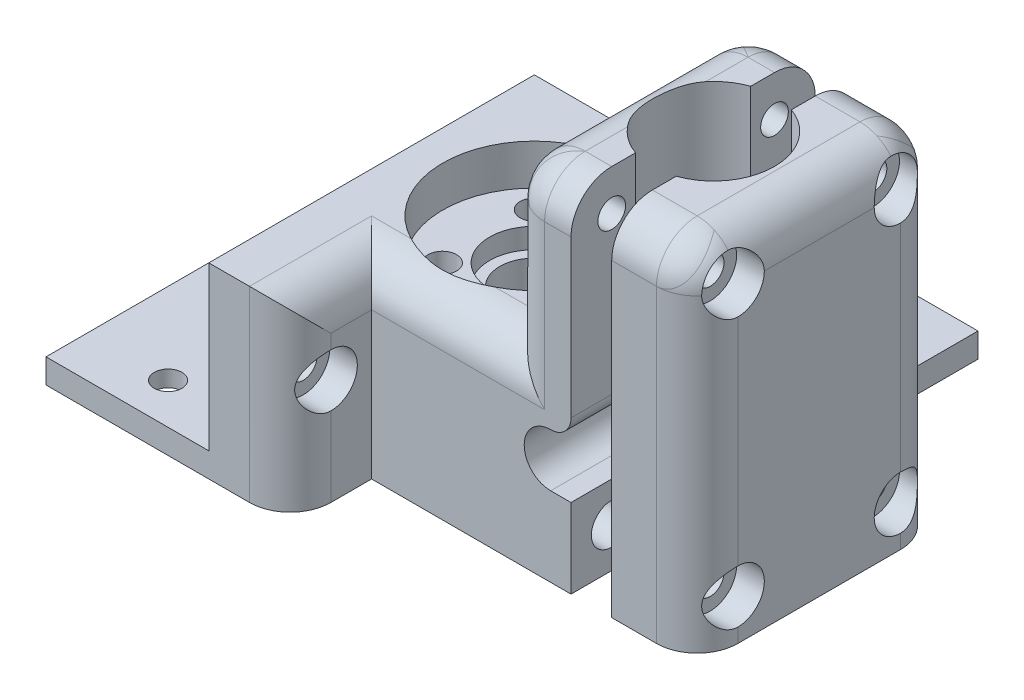
SolidWorks part; units mm, degrees
material "ABS"
ref_plane "Front Plane" through (0, 0, 0) normal (0, 0, 1) x (1, 0, 0)
ref_plane "Top Plane" through (0, 0, 0) normal (0, 1, 0) x (1, 0, 0)
ref_plane "Right Plane" through (0, 0, 0) normal (1, 0, 0) x (0, 0, -1)
sketch "Sketch1" plane through (0, 0, 0) normal (1, 0, 0) x (0, 0, -1)
  line L1 (-15, -10) -> (15, -10)
  line L2 (-15, -10) -> (-15, 10)
  line L3 (-15, 10) -> (15, 10)
  line L4 (15, -10) -> (15, 10)
  line L5 (-15, -10) -> (15, 10) construction
  line L6 (-15, 10) -> (15, -10) construction
  point P0 (0, 0)
  dimension "D1" = 30
  dimension "D2" = 20
extrude "Boss-Extrude1" add sketch "Sketch1" along normal blind 50
sketch "Sketch2" plane through (0, 10, 0) normal (0, 1, 0) x (1, 0, 0)
  line L0 (0, 15) -> (0, -15) construction
  circle A0 centre (15, 0) radius 4.25
  circle A1 centre (37, 0) radius 7.5
  dimension "D1" = 8.5
  dimension "D3" = 15
  dimension "D2" = 22
  dimension "D4" = 15
extrude "Cut-Extrude1" cut sketch "Sketch2" against normal through all
sketch "Sketch4" plane through (0, 10, 0) normal (0, 1, 0) x (1, 0, 0)
  circle A0 centre (15, 0) radius 11.25
  dimension "D1" = 22.5
extrude "Cut-Extrude3" cut sketch "Sketch4" against normal blind 5
sketch "Sketch5" plane through (0, 5, 0) normal (0, 1, 0) x (1, 0, 0)
  line L1 (20.6569, -5.6569) -> (9.3431, -5.6569) construction
  line L2 (20.6569, -5.6569) -> (20.6569, 5.6569) construction
  line L3 (20.6569, 5.6569) -> (9.3431, 5.6569) construction
  line L4 (9.3431, -5.6569) -> (9.3431, 5.6569) construction
  line L5 (20.6569, -5.6569) -> (9.3431, 5.6569) construction
  line L6 (20.6569, 5.6569) -> (9.3431, -5.6569) construction
  circle A3 centre (9.3431, -5.6569) radius 1.75
  circle A4 centre (9.3431, 5.6569) radius 1.75
  circle A5 centre (20.6569, 5.6569) radius 1.75
  circle A6 centre (20.6569, -5.6569) radius 1.75
  point P0 (15, 0)
  dimension "D1" = 16
  dimension "D3" = 3.5
  dimension "D4" = 3.5
  dimension "D5" = 3.5
  dimension "D6" = 3.5
extrude "Cut-Extrude4" cut sketch "Sketch5" against normal through all
sketch "Sketch6" plane through (0, -10, 0) normal (0, -1, 0) x (1, 0, 0)
  line L1 (12.8058, 5.7559) -> (10.9887, 8.7052)
  line L2 (10.9887, 8.7052) -> (7.526, 8.6061)
  line L3 (7.526, 8.6061) -> (5.8805, 5.5578)
  line L4 (5.8805, 5.5578) -> (7.6976, 2.6085)
  line L5 (7.6976, 2.6085) -> (11.1603, 2.7076)
  line L6 (11.1603, 2.7076) -> (12.8058, 5.7559)
  line L7 (17.1942, 5.7559) -> (18.8397, 2.7076)
  line L8 (18.8397, 2.7076) -> (22.3024, 2.6085)
  line L9 (22.3024, 2.6085) -> (24.1195, 5.5578)
  line L10 (24.1195, 5.5578) -> (22.474, 8.6061)
  line L11 (22.474, 8.6061) -> (19.0113, 8.7052)
  line L12 (19.0113, 8.7052) -> (17.1942, 5.7559)
  line L13 (24.1197, -5.7506) -> (22.4694, -2.7048)
  line L14 (22.4694, -2.7048) -> (19.0066, -2.6111)
  line L15 (19.0066, -2.6111) -> (17.194, -5.5631)
  line L16 (17.194, -5.5631) -> (18.8443, -8.6089)
  line L17 (18.8443, -8.6089) -> (22.3071, -8.7026)
  line L18 (22.3071, -8.7026) -> (24.1197, -5.7506)
  line L19 (12.8058, -5.7559) -> (11.1603, -2.7076)
  line L20 (11.1603, -2.7076) -> (7.6976, -2.6085)
  line L21 (7.6976, -2.6085) -> (5.8805, -5.5578)
  line L22 (5.8805, -5.5578) -> (7.526, -8.6061)
  line L23 (7.526, -8.6061) -> (10.9887, -8.7052)
  line L24 (10.9887, -8.7052) -> (12.8058, -5.7559)
  circle A0 centre (9.3431, 5.6569) radius 3 construction
  circle A1 centre (20.6569, 5.6569) radius 3 construction
  circle A2 centre (20.6569, -5.6569) radius 3 construction
  circle A3 centre (9.3431, -5.6569) radius 3 construction
  dimension "D1" = 6
  dimension "D2" = 6
  dimension "D4" = 6
  dimension "D3" = 6
extrude "Cut-Extrude5" cut sketch "Sketch6" against normal blind 6
ref_plane "Plane1" through (0, 0, 0) normal (0, 0, -1) x (-1, 0, 0)
sketch "Sketch7" plane through (0, 0, 15) normal (0, 0, 1) x (1, 0, 0)
  line L0 (50, -10) -> (0, -10) construction
  line L1 (0, 10) -> (10, 10)
  line L2 (0, 10) -> (0, -10)
  line L3 (0, -10) -> (10, -10)
  line L4 (10, 10) -> (10, -10)
  dimension "D1" = 10
extrude "Boss-Extrude2" add sketch "Sketch7" along normal blind 10
hole_wizard "CBORE for M3 Hex Socket Head Cap Screw4" positions "Sketch16" profile "Sketch17" counterbore size "M3" standard "ISO" end condition through all
sketch "Sketch16" plane through (10, 0, 0) normal (1, 0, 0) x (0, 0, -1)
  line L0 (-25, -10) -> (-25, 10) construction
  point P0 (-20, 0)
  dimension "D1" = 5
sketch "Sketch17" plane through (10, 0, 20) normal (0, 1, 0) x (0, 0, -1)
  line L0 (0, 0) -> (0, 10)
  line L1 (0, 10) -> (1.7, 10)
  line L3 (1.7, 10) -> (1.7, 3.4)
  line L4 (1.7, 3.4) -> (3.25, 3.4)
  line L5 (3.25, 3.4) -> (3.25, 0)
  line L7 (3.25, 0) -> (0, 0)
  line L11 (0, -6.35) -> (0, 107.95) construction
  dimension "Thru Hole Dia." = 3.4
  dimension "Thru Hole Depth" = 10
  dimension "C'Bore Dia." = 6.5
  dimension "C'Bore Depth" = 3.4
sketch "Sketch19" plane through (0, 5, 0) normal (0, 1, 0) x (1, 0, 0)
  circle A0 centre (15, 0) radius 5.5
  dimension "D1" = 11
extrude "Cut-Extrude10" cut sketch "Sketch19" against normal blind 2.5
hole_wizard "CBORE for M3 Hex Socket Head Cap Screw5" positions "Sketch22" profile "Sketch24" counterbore size "M3" standard "ISO" end condition through all
sketch "Sketch22" plane through (0, 0, 15) normal (0, 0, 1) x (1, 0, 0)
  line L0 (50, -10) -> (10, -10) construction
  point P0 (32, 0)
  dimension "D1" = 10
  dimension "D2" = 2.5
sketch "Sketch24" plane through (32, 0, 15) normal (1, 0, 0) x (0, -1, 0)
  line L0 (0, 0) -> (0, 30)
  line L1 (0, 30) -> (1.7, 30)
  line L3 (1.7, 30) -> (1.7, 26.4)
  line L4 (1.7, 26.4) -> (3.25, 26.4)
  line L5 (3.25, 26.4) -> (3.25, 0)
  line L7 (3.25, 0) -> (0, 0)
  line L11 (0, -6.35) -> (0, 107.95) construction
  dimension "Thru Hole Dia." = 3.4
  dimension "Thru Hole Depth" = 30
  dimension "C'Bore Dia." = 6.5
  dimension "C'Bore Depth" = 26.4
sketch "Sketch26" plane through (0, 10, 0) normal (0, 1, 0) x (1, 0, 0)
  line L0 (50, 15) -> (0, 15) construction
  line L1 (50, -15) -> (26.25, -15)
  line L2 (50, -15) -> (50, 15)
  line L3 (50, 15) -> (26.25, 15)
  line L4 (26.25, -15) -> (26.25, 15)
  circle A0 centre (15, 0) radius 11.25 construction
extrude "Boss-Extrude3" add sketch "Sketch26" along normal blind 20
sketch "Sketch43" plane through (0, -10, 0) normal (0, -1, 0) x (1, 0, 0)
  line L6 (0, 25) -> (0, -15)
  line L7 (0, -15) -> (50, -15)
  line L8 (50, -15) -> (50, 15)
  line L9 (50, 15) -> (10, 15)
  line L10 (10, 15) -> (10, 25)
  line L11 (10, 25) -> (0, 25)
  line L12 (0, 25) -> (0, -15)
  line L13 (0, -15) -> (50, -15)
  line L14 (50, -15) -> (50, 15)
  line L15 (50, 15) -> (10, 15)
  line L16 (10, 15) -> (10, 25)
  line L17 (10, 25) -> (0, 25)
  line L37 (10.9887, 8.7052) -> (7.526, 8.6061)
  line L38 (7.526, 8.6061) -> (5.8805, 5.5578)
  line L39 (5.8805, 5.5578) -> (7.6976, 2.6085)
  line L40 (7.6976, 2.6085) -> (11.1603, 2.7076)
  line L41 (11.1603, 2.7076) -> (12.8058, 5.7559)
  line L42 (12.8058, 5.7559) -> (10.9887, 8.7052)
  line L43 (22.474, 8.6061) -> (19.0113, 8.7052)
  line L44 (19.0113, 8.7052) -> (17.1942, 5.7559)
  line L45 (17.1942, 5.7559) -> (18.8397, 2.7076)
  line L46 (18.8397, 2.7076) -> (22.3024, 2.6085)
  line L47 (22.3024, 2.6085) -> (24.1195, 5.5578)
  line L48 (24.1195, 5.5578) -> (22.474, 8.6061)
  line L49 (22.4694, -2.7048) -> (19.0066, -2.6111)
  line L50 (19.0066, -2.6111) -> (17.194, -5.5631)
  line L51 (17.194, -5.5631) -> (18.8443, -8.6089)
  line L52 (18.8443, -8.6089) -> (22.3071, -8.7026)
  line L53 (22.3071, -8.7026) -> (24.1197, -5.7506)
  line L54 (24.1197, -5.7506) -> (22.4694, -2.7048)
  line L55 (11.1603, -2.7076) -> (7.6976, -2.6085)
  line L56 (7.6976, -2.6085) -> (5.8805, -5.5578)
  line L57 (5.8805, -5.5578) -> (7.526, -8.6061)
  line L58 (7.526, -8.6061) -> (10.9887, -8.7052)
  line L59 (10.9887, -8.7052) -> (12.8058, -5.7559)
  line L60 (12.8058, -5.7559) -> (11.1603, -2.7076)
  circle A0 centre (9.3431, 5.6569) radius 3 construction
  circle A1 centre (20.6569, 5.6569) radius 3 construction
  circle A2 centre (20.6569, -5.6569) radius 3 construction
  circle A3 centre (9.3431, -5.6569) radius 3 construction
  circle A4 centre (15, 0) radius 4.25
  circle A5 centre (37, 0) radius 7.5
  dimension "D1" = 0
extrude "downextrude-forsupport" add sketch "Sketch43" along normal blind 3
sketch "Sketch44" plane through (0, 0, -15) normal (0, 0, -1) x (-1, 0, 0)
  line L6 (0, -13) -> (-34.5, -13)
  line L7 (0, -13) -> (0, -10)
  line L8 (0, -10) -> (-34.5, -10)
  line L9 (-34.5, -13) -> (-34.5, -10)
  dimension "D1" = 34.5
  dimension "D2" = 3
extrude "outwards-forsupport" add sketch "Sketch44" along normal blind 20
sketch "Sketch45" plane through (0, 0, 0) normal (-1, 0, 0) x (0, 0, 1)
  line L1 (-35, -10) -> (25, -10)
  line L2 (-35, -10) -> (-35, -13)
  line L3 (-35, -13) -> (25, -13)
  line L4 (25, -10) -> (25, -13)
extrude "outwards2-forsupport" add sketch "Sketch45" along normal blind 20
sketch "Sketch28" plane through (0, 10, 0) normal (0, -1, 0) x (1, 0, 0)
  circle A0 centre (37, 0) radius 7.5
extrude "Cut-Extrude12" cut sketch "Sketch28" against normal through all
hole_wizard "CBORE for M3 Hex Socket Head Cap Screw6" positions "Sketch32" profile "Sketch33" counterbore size "M3" standard "ISO"
sketch "Sketch32" plane through (50, 0, 0) normal (1, 0, 0) x (0, 0, -1)
  line L1 (-15, 30) -> (15, 30) construction
  line L2 (-15, 30) -> (-15, -13) construction
  line L3 (15, -13) -> (-15, -13) construction
  point P0 (-10, 25)
  point P2 (-10, -8)
  dimension "D1" = 5
  dimension "D2" = 5
  dimension "D3" = 5
  dimension "D4" = 5
sketch "Sketch33" plane through (50, 25, 10) normal (0, 1, 0) x (0, 0, -1)
  line L0 (0, 0) -> (0, 28.0215)
  line L1 (0, 28.0215) -> (1.7, 27)
  line L2 (1.7, 27) -> (1.7, 3.4)
  line L3 (1.7, 3.4) -> (3.25, 3.4)
  line L4 (3.25, 3.4) -> (3.25, 0)
  line L5 (3.25, 0) -> (0, 0)
  line L10 (0, 28.0215) -> (-1.7, 27) construction
  line L11 (0, -6.35) -> (0, 107.95) construction
  dimension "Hole Dia." = 3.4
  dimension "Hole Depth" = 27
  dimension "C'Bore Dia." = 6.5
  dimension "C'Bore Depth" = 3.4
  dimension "Drill Angle" = 118
sketch "Sketch48" plane through (26.25, 0, 0) normal (-1, 0, 0) x (0, 0, 1)
  circle A0 centre (10, 25) radius 2.5
  dimension "D1" = 5
extrude "Cut-Extrude17" cut sketch "Sketch48" against normal blind 4
mirror "Mirror1" about plane through (0, 0, 0) normal (0, 0, -1) of "Cut-Extrude17", "CBORE for M3 Hex Socket Head Cap Screw6"
fillet "Fillet3" radius 5 8 edges at (10, -1.5, 25) (26.25, 20, -15) (38.125, 30, -15) (50, 30, 0) (38.125, 30, 15) (26.25, 20, 15) (18.125, 10, 15) (10, 10, 20)
fillet "Fillet4" radius 5 7 edges at (27.7145, 28.5355, -13.5355) (27.7145, 28.5355, 13.5355) (48.5355, 28.5355, 13.5355) (26.25, 30, 0) (50, 6, 15) (48.5355, 28.5355, -13.5355) (50, 6, -15)
sketch "Sketch29" plane through (0, 30, 0) normal (0, 1, 0) x (1, 0, 0)
  line L0 (50, 15) -> (26.25, 15) construction
  line L1 (34.5, -15) -> (39.5, -15)
  line L2 (34.5, -15) -> (34.5, 15)
  line L3 (34.5, 15) -> (39.5, 15)
  line L4 (39.5, -15) -> (39.5, 15)
  line L5 (34.5, -15) -> (39.5, 15) construction
  line L6 (34.5, 15) -> (39.5, -15) construction
  point P0 (37, 0)
  dimension "D1" = 5
extrude "Cut-Extrude13" cut sketch "Sketch29" against normal through all
hole_wizard "CBORE for M3 Hex Socket Head Cap Screw8" positions "Sketch46" profile "Sketch47" counterbore size "M3" standard "ISO" end condition through all
sketch "Sketch46" plane through (0, -13, 0) normal (0, -1, 0) x (-1, 0, 0)
  line L0 (-34.5, 35) -> (-34.5, 7.0711) construction
  line L1 (-34.5, 35) -> (20, 35) construction
  line L2 (20, 35) -> (20, -25) construction
  line L3 (-5, -25) -> (20, -25) construction
  point P0 (-29.5, 25)
  point P2 (10, 25)
  point P4 (10, -20)
  point P13 (-29.5, 27.5545)
  dimension "D1" = 5
  dimension "D2" = 10
  dimension "D3" = 10
  dimension "D4" = 10
  dimension "D5" = 10
  dimension "D6" = 5
sketch "Sketch47" plane through (29.5, -13, -25) normal (1, 0, 0) x (0, 0, -1)
  line L0 (0, 0) -> (0, 43)
  line L1 (0, 43) -> (1.7, 43)
  line L3 (1.7, 43) -> (1.7, 1)
  line L4 (1.7, 1) -> (3.25, 1)
  line L5 (3.25, 1) -> (3.25, 0)
  line L7 (3.25, 0) -> (0, 0)
  line L11 (0, -6.35) -> (0, 107.95) construction
  dimension "Thru Hole Dia." = 3.4
  dimension "Thru Hole Depth" = 43
  dimension "C'Bore Dia." = 6.5
  dimension "C'Bore Depth" = 1
sketch "Sketch49" plane through (34.5, 0, 0) normal (1, 0, 0) x (0, 0, -1)
  circle A0 centre (-10, -8) radius 2.5
  circle A1 centre (10, -8) radius 2.5
  dimension "D1" = 5
  dimension "D2" = 5
extrude "Cut-Extrude18" cut sketch "Sketch49" against normal blind 4
sketch "Sketch50" plane through (0, 0, 15) normal (0, 0, 1) x (1, 0, 0)
  line L3 (34.5, -13) -> (34.5, -2.0767) construction
  line L4 (34.5, -3.25) -> (32, -3.25)
  line L5 (32, -3.25) -> (32, 3.25)
  line L6 (34.5, 2.0767) -> (34.5, 25) construction
  line L7 (34.5, 5.75) -> (34.5, -3.25)
  arc A0 (34.5, 2.0767) -> (34.5, -2.0767) centre (32, 0) ccw construction
  arc A1 (32, 3.25) -> (34.5, 5.75) centre (32, 5.75) ccw
extrude "Cut-Extrude19" cut sketch "Sketch50" against normal up to surface (26.4 mm away) up to face at (33.7, 0, -11.4)
